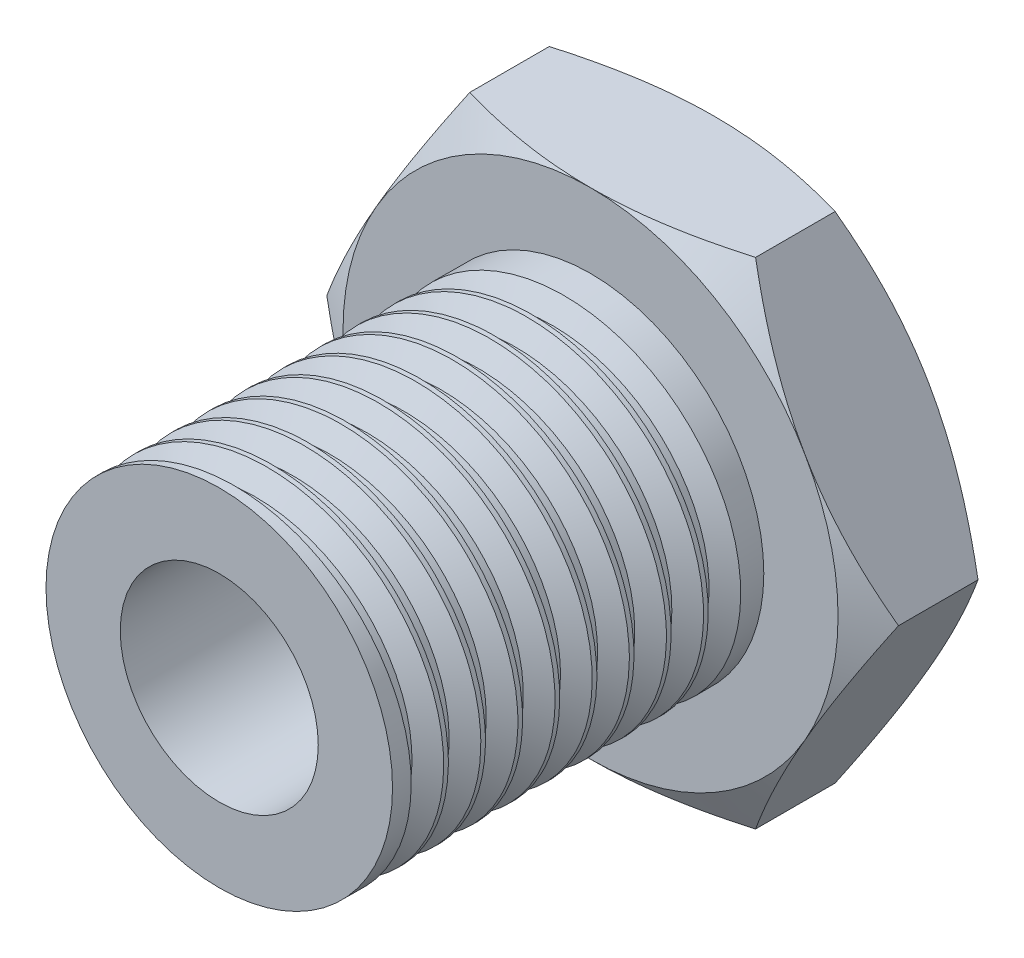
SolidWorks part; units mm, degrees
ref_plane "前视基准面" through (0, 0, 0) normal (0, 0, 1) x (1, 0, 0)
ref_plane "上视基准面" through (0, 0, 0) normal (0, 1, 0) x (1, 0, 0)
ref_plane "右视基准面" through (0, 0, 0) normal (1, 0, 0) x (0, 0, -1)
sketch "草图2" plane through (0, 0, 0) normal (0, 0, 1) x (1, 0, 0)
  line L1 (11.547, 0) -> (5.7735, 10)
  line L2 (5.7735, 10) -> (-5.7735, 10)
  line L3 (-5.7735, 10) -> (-11.547, 0)
  line L4 (-11.547, 0) -> (-5.7735, -10)
  line L5 (-5.7735, -10) -> (5.7735, -10)
  line L6 (5.7735, -10) -> (11.547, 0)
  circle A0 centre (0, 0) radius 10 construction
  dimension "D1" = 20
extrude "凸台-拉伸1" add sketch "草图2" along normal blind 5
sketch "草图3" plane through (0, 0, 5) normal (0, 0, 1) x (1, 0, 0)
  circle A0 centre (0, 0) radius 7
  dimension "D1" = 14
extrude "凸台-拉伸2" add sketch "草图3" along normal blind 15
thread "螺纹线1" pitch 1.5 method cut profile "螺纹线轮廓1" start angle 0, offset 0, length 13, pitch 1.5, diameter 14
ref_plane "基准面1" through (-7, 0, 20) normal (0, -1, 0) x (-1, 0, 0)
sketch "螺纹线轮廓1" plane through (-7, 0, 20) normal (0, -1, 0) x (-1, 0, 0)
  line L0 (0, 0) -> (0, 1.5) construction
  line L11 (0, 0) -> (0, 1.3125)
  line L12 (0, 1.3125) -> (-0.8119, 0.8437)
  line L13 (-0.8119, 0.8437) -> (-0.8119, 0.4687)
  line L15 (-0.8119, 0.4687) -> (0, 0)
  line L17 (-0.8119, 0.6562) -> (0, 0.6562) construction
  point P2 (0, 0)
  dimension "Pitch" = 1.5
  dimension "Profile_Angle" = 60
  dimension "Profile_Land" = 0.375
  dimension "Profile_Height" = 0.8119
sketch "草图6" plane through (0, 0, 0) normal (0, 1, 0) x (1, 0, 0)
  line L0 (0, 2.6656) -> (0, -4.229) construction
  line L1 (-11.547, 0) -> (-10, 0)
  line L2 (-5.7735, 0) -> (-11.547, 0) construction
  line L3 (-10, 0) -> (-11.547, -0.8932)
  line L4 (-11.547, -5) -> (-11.547, 0) construction
  line L5 (-11.547, -0.8932) -> (-11.547, 0)
  line L6 (-11.547, -4.1068) -> (-10, -5)
  line L7 (-5.7735, -5) -> (-11.547, -5) construction
  line L8 (-10, -5) -> (-11.547, -5)
  line L9 (-11.547, -5) -> (-11.547, -4.1068)
  dimension "D1" = 10
  dimension "D2" = 30
  dimension "D3" = 30
revolve "切除-旋转1" cut sketch "草图6" angle 360 about L0
sketch "草图7" plane through (0, 0, 0) normal (0, 0, -1) x (-1, 0, 0)
  circle A0 centre (0, 0) radius 4
  dimension "D1" = 8
extrude "切除-拉伸1" cut sketch "草图7" against normal through all
